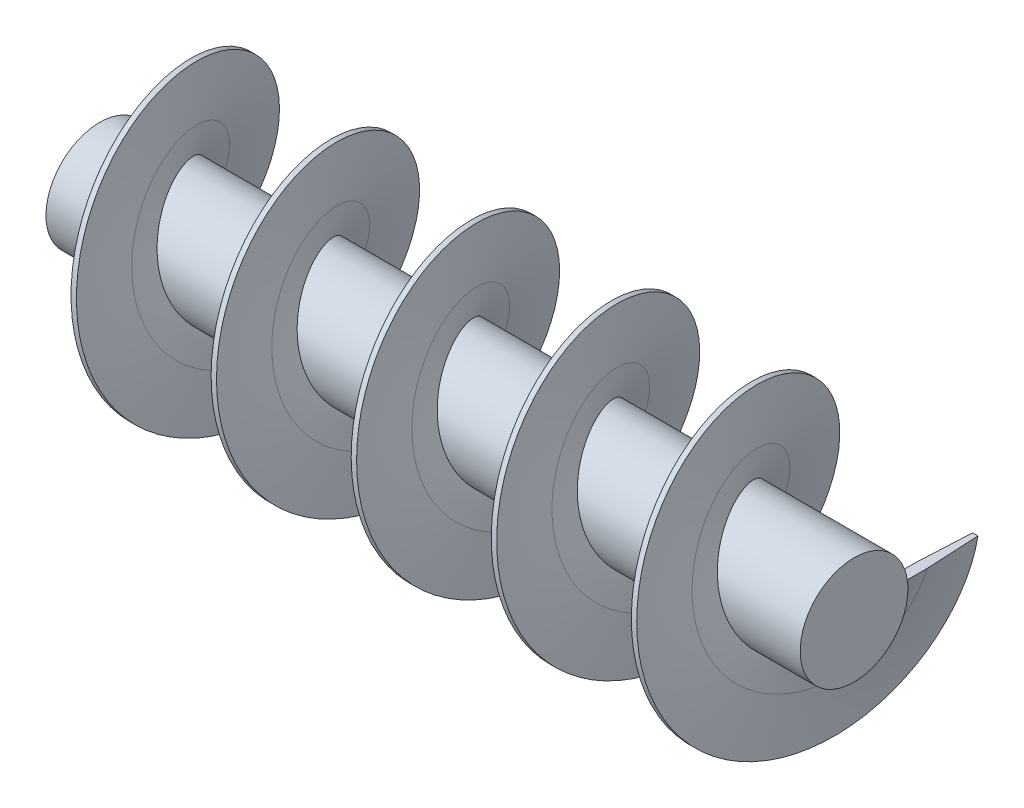
SolidWorks part; units mm, degrees
ref_plane "Front Plane" through (0, 0, 0) normal (0, 0, 1) x (1, 0, 0)
ref_plane "Top Plane" through (0, 0, 0) normal (0, 1, 0) x (1, 0, 0)
ref_plane "Right Plane" through (0, 0, 0) normal (1, 0, 0) x (0, 0, -1)
sketch "Sketch1" plane through (0, 0, 0) normal (1, 0, 0) x (0, 0, -1)
  circle A0 centre (0, 0) radius 12.7
  dimension "D1" = 25.4
extrude "Boss-Extrude1" add sketch "Sketch1" along normal mid plane 177.8
sketch "Sketch5" plane through (-88.9, 0, 0) normal (-1, 0, 0) x (0, 0, 1)
  circle A0 centre (0, 0) radius 25.4
curve "Helix/Spiral1" pitch 33.02 height 173.355 radius 25.4 centre (-88.9, 0, 0) axis (1, 0, 0) start towards (0, 0, 1)
sketch "Sketch6" plane through (0, 0, 0) normal (0, 0, 1) x (1, 0, 0)
  line L0 (-88.9, -12.7) -> (-88.9, -19.05)
  line L1 (-88.9, -19.05) -> (-88.265, -31.75)
  line L2 (-88.265, -31.75) -> (-86.995, -31.75)
  line L3 (-86.995, -31.75) -> (-86.36, -19.05)
  line L4 (-86.36, -19.05) -> (-86.36, -12.7)
  line L5 (-88.9, -12.7) -> (-86.36, -12.7)
  line L6 (-87.63, -22.3524) -> (-87.63, -47.4269) construction
  point P2 (-87.63, -12.7)
  point P7 (-87.63, -31.75)
  dimension "D1" = 12.7
  dimension "D2" = 19.05
  dimension "D3" = 2.54
  dimension "D4" = 1.27
sweep "Sweep1" add profiles "Sketch6" path "Helix/Spiral1"
